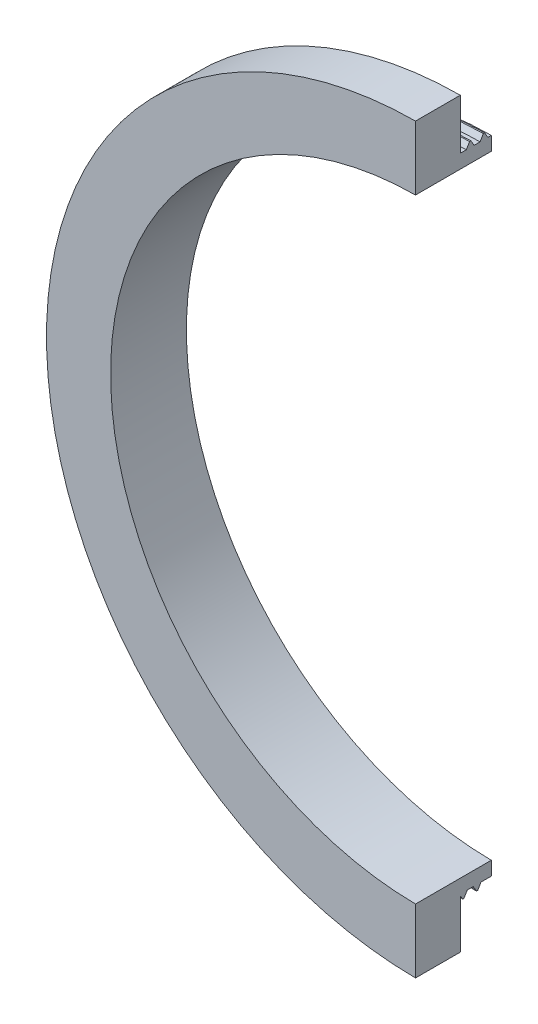
SolidWorks part; units mm, degrees
ref_plane "Front Plane" through (0, 0, 0) normal (0, 0, 1) x (1, 0, 0)
ref_plane "Top Plane" through (0, 0, 0) normal (0, 1, 0) x (1, 0, 0)
ref_plane "Right Plane" through (0, 0, 0) normal (1, 0, 0) x (0, 0, -1)
sketch "Sketch1" plane through (0, 0, 0) normal (0, 0, 1) x (1, 0, 0)
  circle A0 centre (0, 0) radius 53.85
  circle A1 centre (0, 0) radius 44.55
  dimension "D1" = 107.7
  dimension "D2" = 9.3
extrude "Boss-Extrude1" add sketch "Sketch1" along normal blind 6.5
sketch "Sketch2" plane through (0, 0, 0) normal (0, 0, -1) x (-1, 0, 0)
  circle A0 centre (0, 0) radius 44.55 construction
  circle A1 centre (0, 0) radius 44.55
  circle A2 centre (0, 0) radius 46.55
  dimension "D1" = 2
extrude "Boss-Extrude2" add sketch "Sketch2" along normal blind 4.5
thread "Thread1" pitch 1.5 method extrude profile "Thread Profile1" start angle 0, offset 0, length 10, pitch 2, diameter 93.1
ref_plane "Plane1" through (46.55, 0, -4.5) normal (0, -1, 0) x (1, 0, 0)
sketch "Thread Profile1" plane through (46.55, 0, -4.5) normal (0, -1, 0) x (1, 0, 0)
  line L0 (0, 0) -> (0, 1.5) construction
  line L1 (0, 0) -> (0.8119, 0.4687)
  line L2 (0.8119, 0.4687) -> (0.8119, 0.6562)
  line L3 (0.8119, 0.6562) -> (0, 1.125)
  line L4 (0.8119, 0.5625) -> (0, 0.5625) construction
  line L11 (0, 0) -> (0, 1.125)
  point P2 (0, 0)
  dimension "Pitch" = 1.5
  dimension "Profile_Angle" = 60
  dimension "Profile_Land" = 0.1875
  dimension "Profile_Height" = 0.8119
sketch "Sketch5" plane through (0, 0, 6.5) normal (0, 0, 1) x (1, 0, 0)
  line L0 (-0.3, -116.7322) -> (-0.3, 116.7322)
  line L1 (-0.3, 116.7322) -> (99.8343, 116.7322)
  line L2 (-99.8343, 116.7322) -> (-99.8343, -116.7322) construction
  line L3 (-0.3, -116.7322) -> (99.8343, -116.7322)
  line L4 (99.8343, 116.7322) -> (99.8343, -116.7322)
  line L5 (-99.8343, 116.7322) -> (99.8343, -116.7322) construction
  line L6 (-99.8343, -116.7322) -> (99.8343, 116.7322) construction
  point P0 (0, 0)
  point P10 (0.25, 0.2923)
  dimension "D1" = 0.3
extrude "Cut-Extrude1" cut sketch "Sketch5" against normal through all and the other way through all
